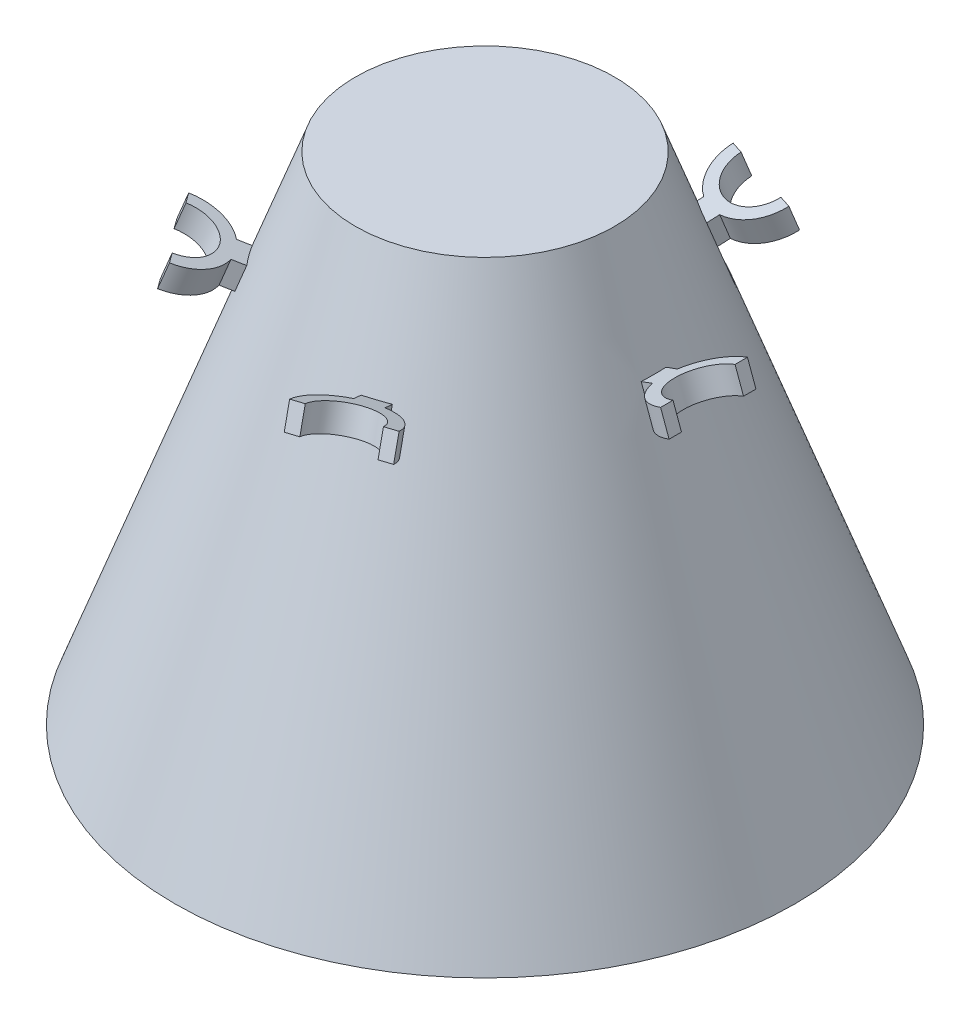
SolidWorks part; units mm, degrees
material "ABS"
ref_plane "Front Plane" through (0, 0, 0) normal (0, 0, 1) x (1, 0, 0)
ref_plane "Top Plane" through (0, 0, 0) normal (0, 1, 0) x (1, 0, 0)
ref_plane "Right Plane" through (0, 0, 0) normal (1, 0, 0) x (0, 0, -1)
sketch "Sketch1" plane through (0, 0, 0) normal (0, 1, 0) x (1, 0, 0)
  circle A0 centre (0, 0) radius 25
  dimension "D1" = 50
extrude "Boss-Extrude1" add sketch "Sketch1" along normal blind 40 draft 20
sketch "Sketch2" plane through (0, 0, 0) normal (0, 0, 1) x (1, 0, 0)
  line L0 (10.4412, 40) -> (13.622, 31.2609) construction
  line L1 (25, 0) -> (10.4412, 40) construction
  line L2 (13.622, 31.2609) -> (18.3204, 32.971)
  line L3 (18.3204, 32.971) -> (19.0045, 31.0916)
  line L4 (19.0045, 31.0916) -> (14.306, 29.3815)
  line L6 (13.622, 31.2609) -> (11.7426, 30.5768)
  line L7 (11.7426, 30.5768) -> (12.4266, 28.6974)
  line L8 (12.4266, 28.6974) -> (14.306, 29.3815)
  dimension "D1" = 5
  dimension "D2" = 2
  dimension "D3" = 2
  dimension "D4" = 9.3
extrude "Boss-Extrude2" add sketch "Sketch2" along normal mid plane 2
sketch "Sketch3" plane through (-8.4536, 23.226, 0) normal (-0.342, 0.9397, 0) x (0.9397, 0.342, 0)
  line L1 (27.7825, 2.5) -> (27.7825, 3.5)
  line L2 (23.4923, 0) -> (27.7825, 0) construction
  line L3 (27.7825, -2.5) -> (27.7825, -3.5)
  circle A0 centre (27.7825, 0) radius 2.5
  circle A1 centre (27.7825, 0) radius 3.5
  ellipse E0 centre (6.7825, 0) end of major axis (-9.9273, 0) minor radius 15.5637 (23.4578, -1) -> (23.4578, 1) ccw construction
  ellipse E1 centre (13.6808, 0) end of major axis (13.6808, -10.4412) minor radius 9.8115 construction
  point P6 (27.7825, 0)
  line M3 (28.4923, 1) -> (23.4578, 1)
  line M5 (23.4578, -1) -> (28.4923, -1)
  line M6 (28.4923, -1) -> (28.4923, 1)
  dimension "D1" = 7
  dimension "D2" = 5
  dimension "D3" = 21
extrude "Boss-Extrude3" add sketch "Sketch3" against normal blind 2 contours L1 A1 A0 M3 | A1 L2 A0 M3 | L2 A1 A0 M5 | A1 L3 A0 M5 region at (16.1052, 32.1647, -2.3206) region at (14.89, 31.7224, -0.505) region at (16.1052, 32.1647, 2.3206) region at (14.89, 31.7224, 0.505)
extrude "Cut-Extrude1" cut sketch "Sketch3<3>" against normal blind 2 contours A0 M5 M3 M6 | A0 M3 M5 M6 region at (19.2686, 33.316, -1.7188) region at (16.8439, 32.4335, 0)
sketch "Sketch3<3>" plane through (-8.4536, 23.226, 0) normal (-0.342, 0.9397, 0) x (0.9397, 0.342, 0) same geometry as "Sketch3"
pattern_circular "CirPattern1" count 5 every 72 about axis through (0, 40, 0) along (0, 1, 0) of "Boss-Extrude2", "Boss-Extrude3", "Cut-Extrude1"
